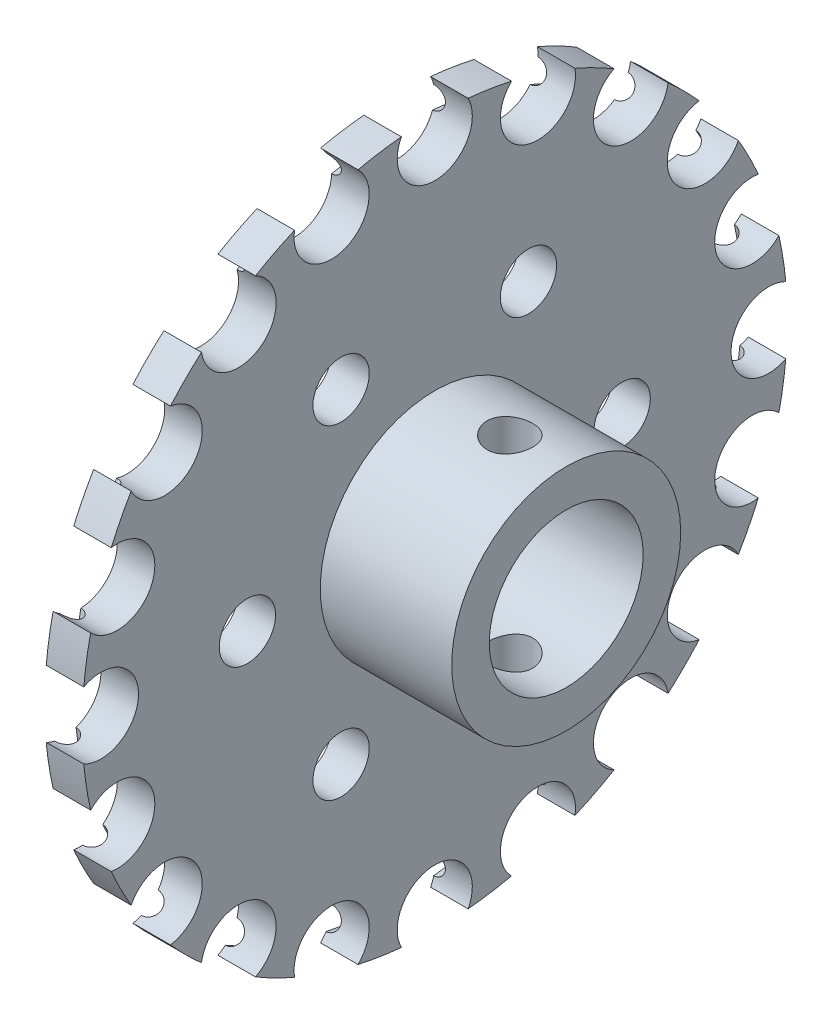
SolidWorks part; units mm, degrees
ref_plane "Front Plane" through (0, 0, 0) normal (0, 0, 1) x (1, 0, 0)
ref_plane "Top Plane" through (0, 0, 0) normal (0, 1, 0) x (1, 0, 0)
ref_plane "Right Plane" through (0, 0, 0) normal (1, 0, 0) x (0, 0, -1)
sketch "Sketch2" plane through (0, 0, 0) normal (1, 0, 0) x (0, 0, -1)
  circle A0 centre (0, 0) radius 20.28 construction
  circle A1 centre (0, 0) radius 4.1
  circle A2 centre (0, 0) radius 17.78 construction
  circle A3 centre (0, 0) radius 18.78
  dimension "D1" = 8.2
  dimension "D2" = 40.56
  dimension "D3" = 1
  dimension "D4" = 2.5
extrude "Boss-Extrude1" add sketch "Sketch2" along normal mid plane 2
sketch "Sketch9" plane through (1, 0, 0) normal (1, 0, 0) x (0, 0, -1)
  circle A0 centre (0, 0) radius 6.1
  circle A1 centre (0, 0) radius 4.1
  circle A2 centre (0, 0) radius 4.1 construction
  dimension "D1" = 2
extrude "Boss-Extrude2" add sketch "Sketch9" along normal blind 7
sketch "Sketch5" plane through (0, 0, 0) normal (0, 1, 0) x (1, 0, 0)
  line L6 (-1, 18.78) -> (-1, -18.78) construction
  line L7 (-1, -18.78) -> (1, -18.78) construction
  circle A0 centre (-1, -17.78) radius 0.5715
  dimension "D1" = 1.143
  dimension "D2" = 1
ref_axis "Axis1" through (8, 0, 0) along (-1, 0, 0)
revolve "Cut-Revolve1" cut sketch "Sketch5" angle 360 about axis through (8, 0, 0) along (-1, 0, 0)
sketch "Sketch7" plane through (-1, 0, 0) normal (-1, 0, 0) x (0, 0, 1)
  circle A0 centre (0, 0) radius 17.78 construction
  circle A1 centre (0, 0) radius 20.28 construction
  dimension "D1" = 40.56
  dimension "D2" = 2.5
sketch "Sketch10" plane through (0, 0, 0) normal (0, 1, 0) x (1, 0, 0)
  line L0 (8, -6.1) -> (8, 6.1) construction
  line L1 (8, 0) -> (-1, 0) construction
  circle A0 centre (5, 0) radius 1.215
  dimension "D1" = 2.43
  dimension "D2" = 3
extrude "Cut-Extrude1" cut sketch "Sketch10" against normal mid plane 20
sketch "Sketch12" plane through (1, 0, 0) normal (1, 0, 0) x (0, 0, -1)
  line L0 (0, 0) -> (-2, -17.78) construction
  line L1 (0, 997.7838) -> (0, 0) construction
  line L6 (0, 0) -> (2, -17.78) construction
  circle A0 centre (0, 0) radius 18.78 construction
  arc A1 (0, 18.78) -> (0, -18.78) centre (0, 0) ccw
  circle A2 centre (0, 0) radius 17.78 construction
  circle A3 centre (0, -17.78) radius 1.5 construction
  circle A4 centre (0, -17.78) radius 2
  dimension "D1" = 1
  dimension "D2" = 3
  dimension "D3" = 0.5
extrude "Cut-Extrude3" cut sketch "Sketch12" against normal mid plane 20 contours A4
pattern_circular "CirPattern1" count 20 over 360 about axis through (8, 0, 0) along (-1, 0, 0) of "Cut-Extrude3"
sketch "Sketch13" plane through (1, 0, 0) normal (1, 0, 0) x (0, 0, -1)
  circle A0 centre (-9.9803, 0) radius 1.5
  dimension "D1" = 3
extrude "Cut-Extrude4" cut sketch "Sketch13" against normal blind 10
pattern_circular "CirPattern2" count 6 over 360 about axis through (8, 0, 0) along (-1, 0, 0) of "Cut-Extrude4"
